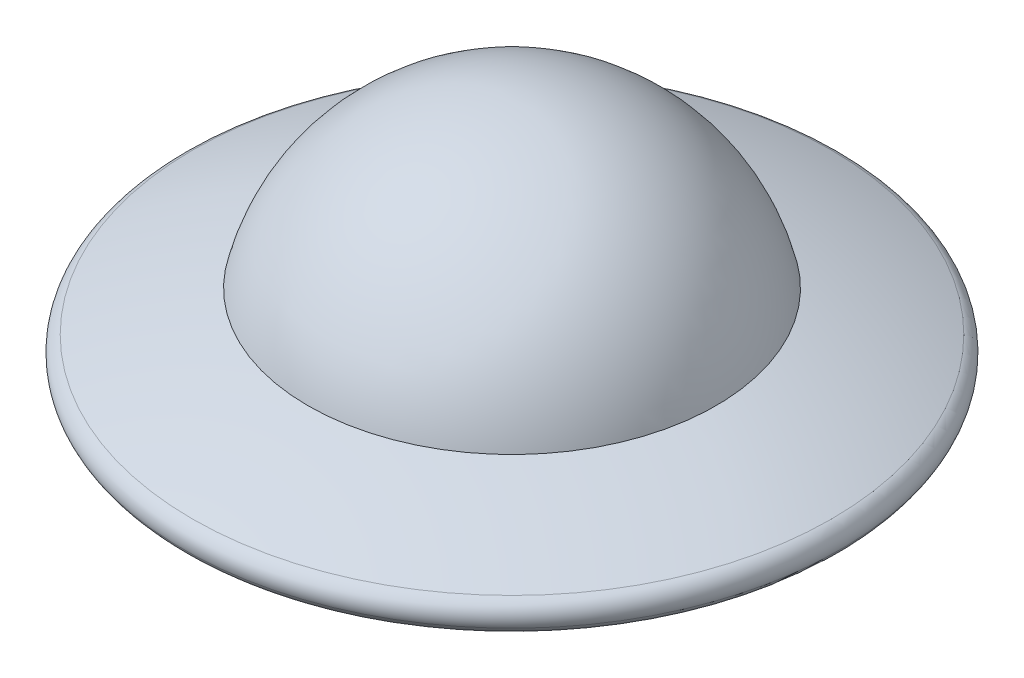
SolidWorks part; units mm, degrees
ref_plane "Front Plane" through (0, 0, 0) normal (0, 0, 1) x (1, 0, 0)
ref_plane "Top Plane" through (0, 0, 0) normal (0, 1, 0) x (1, 0, 0)
ref_plane "Right Plane" through (0, 0, 0) normal (1, 0, 0) x (0, 0, -1)
sketch "Sketch2" plane through (0, 0, 0) normal (1, 0, 0) x (0, 0, -1)
  line L0 (0, 55.5842) -> (0, 0) construction
  line L1 (0, 43.0842) -> (20, 43.0842) construction
  line L2 (20, 43.0842) -> (19.1579, 41.2701)
  line L3 (0, 55.5842) -> (0, 53.5842)
  arc A0 (20, 43.0842) -> (12.1757, 45.913) centre (0, 0) ccw
  arc A1 (12.1757, 45.913) -> (0, 55.5842) centre (0, 43.0842) ccw
  arc A2 (19.1579, 41.2701) -> (10.4307, 44.2883) centre (0, 0) ccw
  arc A3 (10.4307, 44.2883) -> (0, 53.5842) centre (0, 43.0842) ccw
  dimension "D2" = 95
  dimension "D3" = 25
  dimension "D1" = 20
  dimension "D4" = 2
revolve "Revolve2" add sketch "Sketch2" angle 360 about L0
fillet "Fillet1" radius 1 2 edges at (0, 41.2701, 19.1579) (0, 43.0842, 20)
